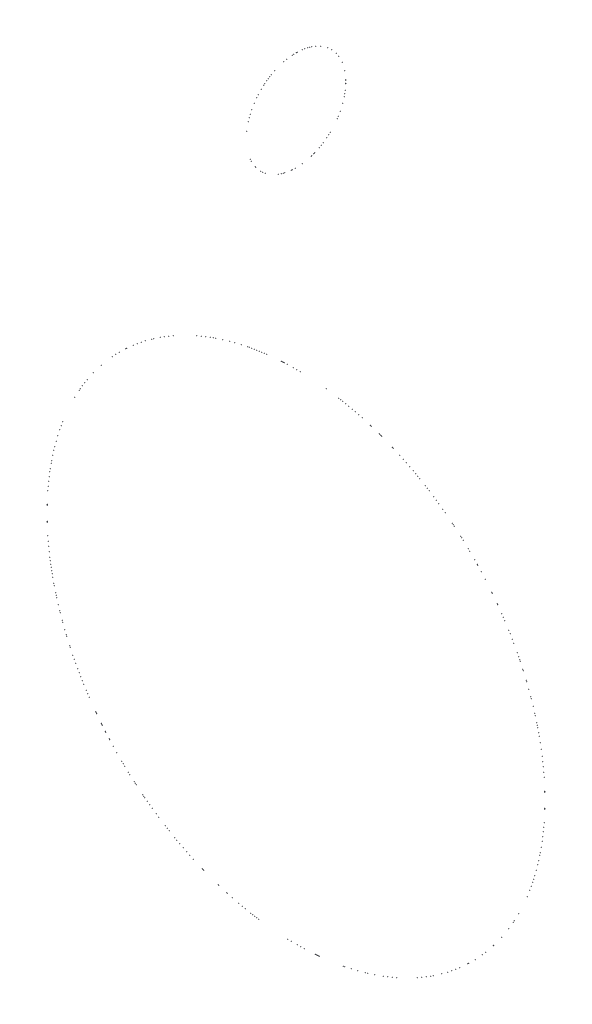
SolidWorks part; units mm, degrees
ref_plane "Piano frontale" through (0, 0, 0) normal (0, 0, 1) x (1, 0, 0)
ref_plane "Piano superiore" through (0, 0, 0) normal (0, 1, 0) x (1, 0, 0)
ref_plane "Piano destro" through (0, 0, 0) normal (1, 0, 0) x (0, 0, -1)
sketch "Schizzo1" plane through (0, 0, 0) normal (0, 0, 1) x (1, 0, 0)
  circle A0 centre (0, 0) radius 10
  dimension "D1" = 20
sketch "Schizzo2" plane through (0, 0, 0) normal (1, 0, 0) x (0, 0, -1)
  circle A0 centre (0, 19) radius 2
  dimension "D1" = 4
  dimension "D2" = 19
extrude "Estrusione-Sottile1" add sketch "Schizzo1" along normal blind 0.001 thin thin type one direction wall 0.001
extrude "Estrusione-Sottile2" add sketch "Schizzo2" along normal blind 0.001 thin thin type one direction wall 0.001
